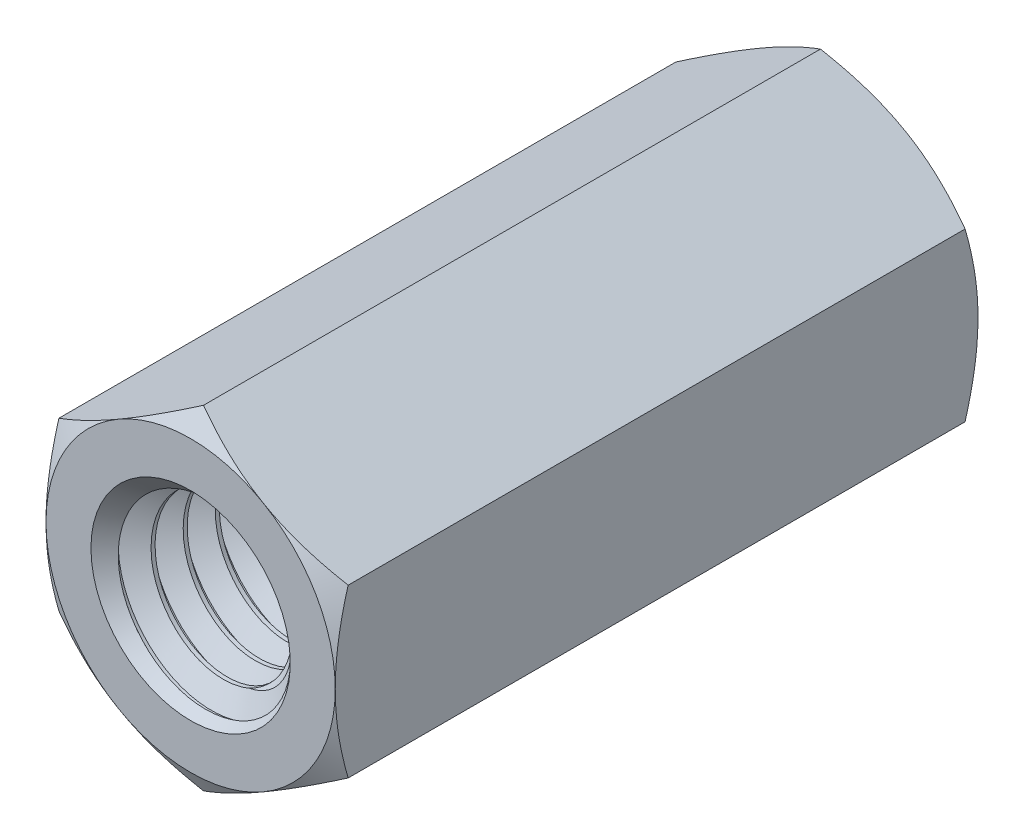
SolidWorks part; units mm, degrees
ref_plane "Front Plane" through (0, 0, 0) normal (0, 0, 1) x (1, 0, 0)
ref_plane "Top Plane" through (0, 0, 0) normal (0, 1, 0) x (1, 0, 0)
ref_plane "Right Plane" through (0, 0, 0) normal (1, 0, 0) x (0, 0, -1)
sketch "Sketch3" plane through (0, 0, 0) normal (1, 0, 0) x (0, 0, -1)
  line L0 (-5, 0) -> (5, 0) construction
  line L1 (0, 2.25) -> (0, -2.25) construction
  line L2 (-5, 1.5) -> (-5, -1.5) construction
  point P2 (-1.3, 0)
  point P3 (1.3, 0)
  dimension "D1" = 6.3
  dimension "Length" = 10
  dimension "Min Thread Length" = 6.3
  dimension "Thread Dia" = 3
  dimension "Hex" = 4.5
sketch "Sketch1" plane through (0, 0, 0) normal (0, 0, 1) x (1, 0, 0)
  line L1 (0, 2.5981) -> (-2.25, 1.299)
  line L2 (-2.25, 1.299) -> (-2.25, -1.299)
  line L3 (-2.25, -1.299) -> (0, -2.5981)
  line L4 (0, -2.5981) -> (2.25, -1.299)
  line L5 (2.25, -1.299) -> (2.25, 1.299)
  line L6 (2.25, 1.299) -> (0, 2.5981)
  circle A0 centre (0, 0) radius 2.25 construction
  circle A1 centre (0, 0) radius 1.5
extrude "Extrude1" add sketch "Sketch1" along normal up to vertex (5 mm away) and the other way up to vertex (5 mm away) up to point (0, 0, 5) other way up to point (0, 0, -5)
sketch "Sketch11" plane through (0, 0, -5) normal (0, 0, -1) x (-1, 0, 0)
  circle A0 centre (0, 0) radius 1.5 construction
  circle A1 centre (0, 0) radius 1.5
curve "Helix/Spiral1" pitch 0.5 height 10.5 radius 1.5 centre (0, 0, -5) axis (0, 0, 1) start towards (0, 1, 0) parameters "Pitch"=0.5
sketch "Sketch12" plane through (0, 0, 0) normal (1, 0, 0) x (0, 0, -1)
  line L0 (5.4375, 1.5) -> (5, 1.5)
  line L1 (5.4375, 1.5) -> (5.25, 1.1752)
  line L2 (5.25, 1.1752) -> (5.1875, 1.1752)
  line L3 (5.1875, 1.1752) -> (5, 1.5)
  line L4 (5.2188, 1.1752) -> (5.2188, 1.5) construction
  line L5 (5.3438, 1.3376) -> (5.0938, 1.3376) construction
  dimension "D1" = 0.0625
  dimension "D2" = 0.25
  dimension "D3" = 60
sweep "Sweep1" add profiles "Sketch12" path "Helix/Spiral1"
sketch "Sketch6" plane through (0, 0, -5) normal (0, 0, -1) x (-1, 0, 0)
  line L6 (0, 2.5981) -> (-2.25, 1.299)
  line L7 (-2.25, 1.299) -> (-2.25, -1.299)
  line L8 (-2.25, -1.299) -> (0, -2.5981)
  line L9 (0, -2.5981) -> (2.25, -1.299)
  line L10 (2.25, -1.299) -> (2.25, 1.299)
  line L11 (2.25, 1.299) -> (0, 2.5981)
  line L12 (0, 2.5981) -> (-2.25, 1.299)
  line L13 (-2.25, 1.299) -> (-2.25, -1.299)
  line L14 (-2.25, -1.299) -> (0, -2.5981)
  line L15 (0, -2.5981) -> (2.25, -1.299)
  line L16 (2.25, -1.299) -> (2.25, 1.299)
  line L17 (2.25, 1.299) -> (0, 2.5981)
  dimension "D1" = 0
extrude "Extrude2" cut sketch "Sketch6" along normal through all
sketch "Sketch7" plane through (0, 0, -5) normal (0, 0, -1) x (-1, 0, 0)
  circle A2 centre (0, 0) radius 1.5508
  circle A3 centre (0, 0) radius 1.5508
  dimension "D1" = 0.0508
extrude "Extrude3" cut sketch "Sketch7" against normal through all draft 43
sketch "Sketch8" plane through (0, 0, -5) normal (0, 0, -1) x (-1, 0, 0)
  circle A0 centre (0, 0) radius 2.25 construction
  circle A1 centre (0, 0) radius 2.25
extrude "Extrude4" cut sketch "Sketch8" against normal through all draft 60 flip side to cut
mirror "Mirror1" about plane through (0, 0, 0) normal (0, 0, 1) of "Extrude2", "Extrude3", "Extrude4"
sketch "Sketch9" [suppressed] plane through (0, 0, 0) normal (1, 0, 0) x (0, 0, -1)
  line L1 (-3.7, 1.5508) -> (3.7, 1.5508)
  line L2 (-3.7, 1.5508) -> (-3.7, 0)
  line L3 (-3.7, 0) -> (3.7, 0)
  line L4 (3.7, 1.5508) -> (3.7, 0)
  line L7 (-10, 0) -> (10, 0) construction
revolve "Revolve" [suppressed] add sketch "Sketch9" angle 360 about L0
sketch "Sketch10" [suppressed] plane through (0, 0, 0) normal (1, 0, 0) x (0, 0, -1)
  line L0 (10, 1.5) -> (3.7, 1.5)
  line L1 (-10, 1.5) -> (-3.7, 1.5)
  line L2 (3.7, 1.5) -> (3.7, -1.5)
  line L3 (-10, -1.5508) -> (-3.7, -1.5508)
  line L4 (-3.7, 1.5) -> (-3.7, -1.5508)
  line L5 (3.7, -1.5) -> (10, -1.5)
equation "\"D1@Sketch3\" = \"Min Thread Length@Sketch3\""
equation "\"D3@Helix/Spiral1\" = \"Length@Sketch3\"+\"Pitch@Helix/Spiral1\""
equation "\"D1@Sketch12\" = \"Pitch@Helix/Spiral1\"*.125"
equation "\"D2@Sketch12\" = \"Pitch@Helix/Spiral1\"*.5"
